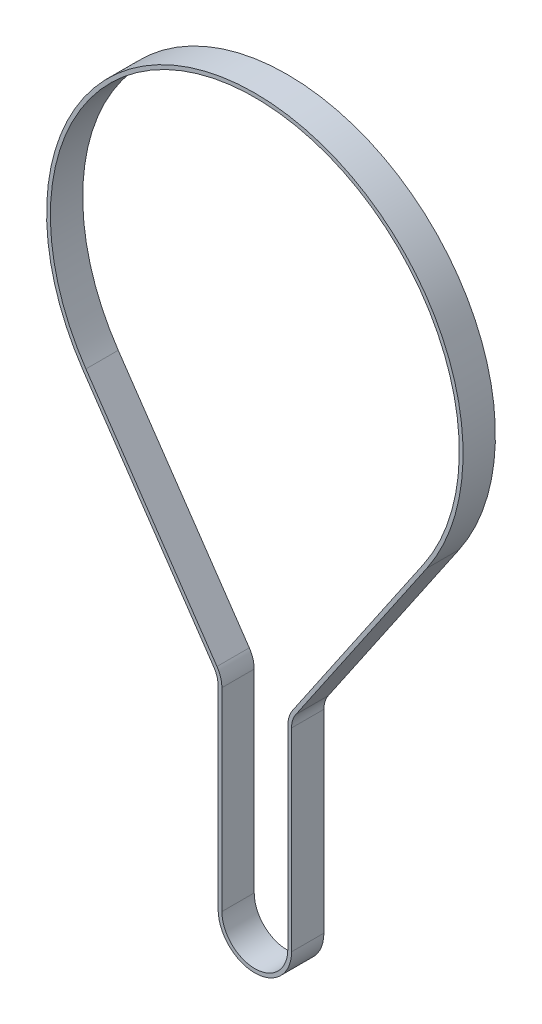
SolidWorks part; units mm, degrees
material "Rubber"
ref_plane "Front Plane" through (0, 0, 0) normal (0, 0, 1) x (1, 0, 0)
ref_plane "Top Plane" through (0, 0, 0) normal (0, 1, 0) x (1, 0, 0)
ref_plane "Right Plane" through (0, 0, 0) normal (1, 0, 0) x (0, 0, -1)
sketch "Sketch1" plane through (0, 0, 0) normal (0, 0, 1) x (1, 0, 0)
  line L10 (-6.3662, 0) -> (-6.3662, 35.9793)
  line L11 (-7.2354, 38.7966) -> (-31.5566, 74.4571)
  line L12 (31.5566, 74.4571) -> (7.2354, 38.7966)
  line L13 (6.3662, 35.9793) -> (6.3662, 0)
  arc A6 (-31.5566, 74.4571) -> (31.5566, 74.4571) centre (0, 95.9793) cw
  arc A7 (-6.3662, 0) -> (6.3662, 0) centre (0, 0) ccw
  arc A8 (-6.3662, 35.9793) -> (-7.2354, 38.7966) centre (-11.3662, 35.9793) ccw
  arc A9 (7.2354, 38.7966) -> (6.3662, 35.9793) centre (11.3662, 35.9793) ccw
  point P0 (0, 0)
  dimension "D8" = 5
  dimension "D9" = 6.3662
  dimension "D10" = 38.1972
  dimension "D3" = 60
  dimension "D2" = 350
sketch "Sketch2" plane through (0, 0, 0) normal (0, 0, 1) x (1, 0, 0)
  line L20 (-6.8162, 35.9793) -> (-6.8162, 0)
  line L21 (6.8162, 0) -> (6.8162, 35.9793)
  line L22 (7.6072, 38.543) -> (31.9284, 74.2035)
  line L23 (-31.9284, 74.2035) -> (-7.6072, 38.543)
  line L24 (-6.1162, 35.9793) -> (-6.1162, 0)
  line L25 (6.1162, 0) -> (6.1162, 35.9793)
  line L26 (7.0289, 38.9374) -> (31.3501, 74.598)
  line L27 (-31.3501, 74.598) -> (-7.0289, 38.9374)
  line L28 (-6.1162, 35.9793) -> (-6.1162, 0)
  line L29 (6.1162, 0) -> (6.1162, 35.9793)
  line L30 (7.0289, 38.9374) -> (31.3501, 74.598)
  line L31 (-31.3501, 74.598) -> (-7.0289, 38.9374)
  arc A16 (-6.8162, 0) -> (6.8162, 0) centre (0, 0) ccw
  arc A17 (7.6072, 38.543) -> (6.8162, 35.9793) centre (11.3662, 35.9793) ccw
  arc A18 (31.9284, 74.2035) -> (-31.9284, 74.2035) centre (0, 95.9793) ccw
  arc A19 (-6.8162, 35.9793) -> (-7.6072, 38.543) centre (-11.3662, 35.9793) ccw
  arc A20 (-6.1162, 35.9793) -> (-7.0289, 38.9374) centre (-11.3662, 35.9793) ccw
  arc A21 (-6.1162, 0) -> (6.1162, 0) centre (0, 0) ccw
  arc A22 (7.0289, 38.9374) -> (6.1162, 35.9793) centre (11.3662, 35.9793) ccw
  arc A23 (31.3501, 74.598) -> (-31.3501, 74.598) centre (0, 95.9793) ccw
  arc A24 (-6.1162, 35.9793) -> (-7.0289, 38.9374) centre (-11.3662, 35.9793) ccw
  arc A25 (-6.1162, 0) -> (6.1162, 0) centre (0, 0) ccw
  arc A26 (7.0289, 38.9374) -> (6.1162, 35.9793) centre (11.3662, 35.9793) ccw
  arc A27 (31.3501, 74.598) -> (-31.3501, 74.598) centre (0, 95.9793) ccw
  dimension "D1" = 0.25
  dimension "D2" = 0.7
extrude "Boss-Extrude1" add sketch "Sketch2" along normal blind 6
